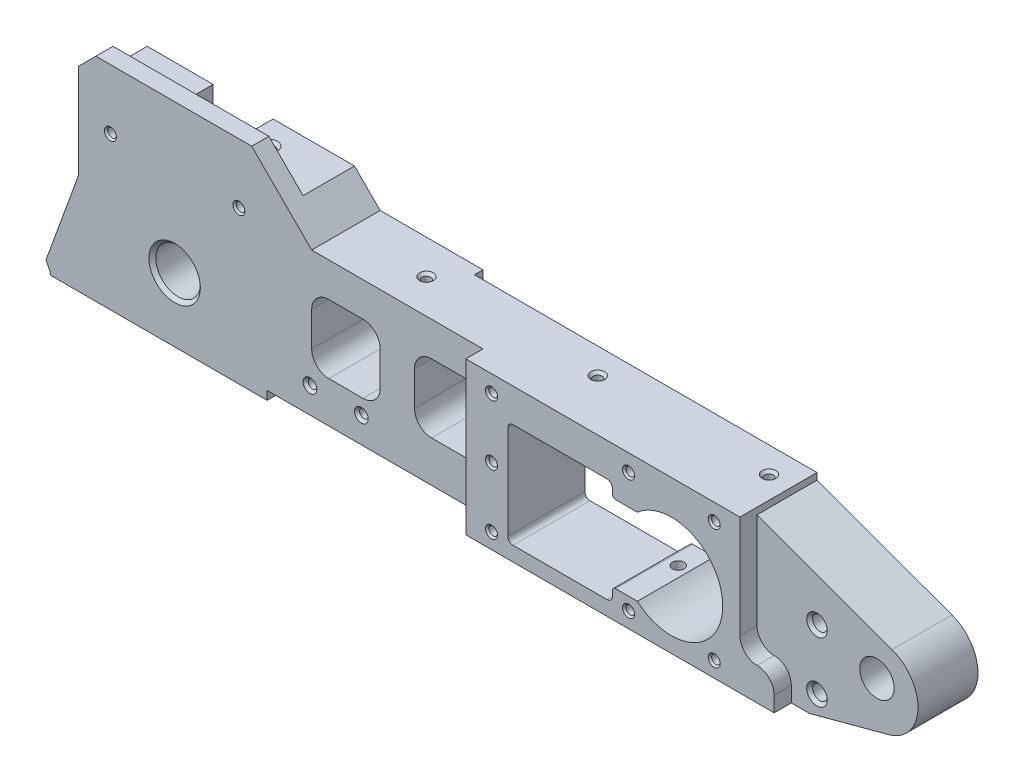
SolidWorks part; units mm, degrees
material "3.0255 (EN-AW 1350A)"
ref_plane "Спереди" through (0, 0, 0) normal (0, 0, 1) x (1, 0, 0)
ref_plane "Сверху" through (0, 0, 0) normal (0, 1, 0) x (1, 0, 0)
ref_plane "Справа" through (0, 0, 0) normal (1, 0, 0) x (0, 0, -1)
sketch "Эскиз5" plane through (0, 0, 0) normal (0, 0, 1) x (1, 0, 0)
  line L1 (45, 40) -> (80, 5)
  line L2 (-56, 40) -> (-56, -25)
  line L3 (-56, -25) -> (-77.8382, -85)
  line L4 (-77.8382, -85) -> (434, -85)
  line L5 (55, 0) -> (-55, 0) construction
  line L6 (434, -85) -> (434, 5)
  line L9 (434, 5) -> (80, 5)
  line L11 (-56, 40) -> (45, 40)
  line L13 (0, -55) -> (0, 55) construction
  circle A0 centre (0, 0) radius 25 construction
  dimension "D6" = 50
  dimension "D2" = 90
  dimension "D3" = 135
  dimension "D4" = 85
  dimension "D7" = 125
  dimension "D8" = 70
  dimension "D9" = 60
  dimension "D10" = 490
  dimension "D11" = 434
  dimension "D12" = 136
extrude "Бобышка-Вытянуть1" add sketch "Эскиз5" along normal mid plane 40
sketch "Эскиз4" plane through (0, 0, -20) normal (0, 0, 1) x (1, 0, 0)
  line L2 (0, 0) -> (0, 50000) construction
  line L4 (-17.5, -25) -> (17.5, -25)
  line L5 (-17.5, 40) -> (-17.5, -25)
  line L6 (45, 40) -> (-56, 40) construction
  line L7 (17.5, 40) -> (17.5, -25)
  point P8 (0, 0)
  line M60 (-56, 40) -> (45, 40)
  dimension "D1" = 35
  dimension "D2" = 65
extrude "Вырез-Вытянуть3" cut sketch "Эскиз4" along normal blind 30 contours L2 L4 L5 M60 | L4 L2 L7 M60 region at (-16.7618, 7.5, -20)
sketch "Эскиз7" plane through (0, 0, 20) normal (0, 0, 1) x (1, 0, 0)
  line L0 (-77.8382, -85) -> (434, -85) construction
  line L1 (434, -85) -> (434, 5) construction
  circle A0 centre (410, -46.6) radius 10.05
  dimension "D3" = 20.1
  dimension "D1" = 38.4
  dimension "D2" = 24
extrude "Вырез-Вытянуть5" cut sketch "Эскиз7" against normal through all
sketch "Эскиз6" plane through (0, 0, 20) normal (0, 0, 1) x (1, 0, 0)
  line L1 (434, 5) -> (80, 5) construction
  line L2 (434, -85) -> (434, 5) construction
  line L3 (434, -26.1873) -> (434, 5)
  line L5 (434, -26.1873) -> (340, 5)
  line L6 (340, 5) -> (434, 5)
  line L7 (410, -46.6) -> (50410, -46.6) construction
  line L8 (434, -67.0127) -> (366.7555, -85)
  line L10 (366.7555, -85) -> (434, -85)
  line L11 (434, -85) -> (434, -67.0127)
  line L12 (-77.8382, -85) -> (434, -85) construction
  line L13 (-56, 40) -> (-56, -25) construction
  dimension "D1" = 396
  dimension "D2" = 31.1873
extrude "Вырез-Вытянуть4" cut sketch "Эскиз6" against normal through all
sketch "Эскиз8" plane through (0, 0, 20) normal (0, 0, 1) x (1, 0, 0)
  line L0 (-77.8382, -85) -> (366.7555, -85) construction
  line L1 (54, -85) -> (354, -85)
  line L2 (54, -85) -> (54, -79)
  line L3 (54, -79) -> (354, -79)
  line L4 (354, -85) -> (354, -79)
  line L5 (-56, 40) -> (-56, -25) construction
  dimension "D1" = 6
  dimension "D2" = 110
  dimension "D3" = 300
extrude "Вырез-Вытянуть6" cut sketch "Эскиз8" against normal through all
sketch "Эскиз9" plane through (0, 0, -20) normal (0, 0, -1) x (-1, 0, 0)
  line L0 (56, 40) -> (56, 20)
  line L1 (56, 40) -> (56, -25) construction
  line L2 (56, 20) -> (-65, 20)
  line L3 (-80, 5) -> (-45, 40) construction
  line L4 (-65, 20) -> (-45, 40)
  line L5 (-45, 40) -> (56, 40)
  dimension "D1" = 20
extrude "Вырез-Вытянуть7" cut sketch "Эскиз9" against normal blind 30
sketch "Эскиз13" plane through (0, 0, -20) normal (0, 0, -1) x (-1, 0, 0)
  line L1 (-204.5, -75.5) -> (-265.5, -75.5)
  line L2 (-204.5, -75.5) -> (-204.5, -14.5)
  line L3 (-204.5, -14.5) -> (-265.5, -14.5)
  line L4 (-265.5, -75.5) -> (-265.5, -67.5)
  line L5 (-204.5, -75.5) -> (-265.5, -14.5) construction
  line L6 (-204.5, -14.5) -> (-265.5, -75.5) construction
  line L7 (-265.5, -22.5) -> (-280.1569, -22.5)
  line L8 (-300, -45) -> (49700, -45) construction
  line L9 (-265.5, -67.5) -> (-280.1569, -67.5)
  line L10 (-265.5, -22.5) -> (-265.5, -14.5)
  arc A0 (-280.1569, -22.5) -> (-280.1569, -67.5) centre (-300, -45) ccw
  circle A1 centre (-235, -45) radius 29 construction
  point P0 (-235, -45)
  point P6 (-235, -45)
  dimension "D7" = 60
  dimension "D8" = 58
  dimension "D1" = 300
  dimension "D2" = 61
  dimension "D3" = 61
  dimension "D4" = 45
  dimension "D5" = 45
  dimension "D6" = 65
extrude "Вырез-Вытянуть8" cut sketch "Эскиз13" against normal through all and the other way through all
sketch "Эскиз16" plane through (0, 0, 20) normal (0, 0, 1) x (1, 0, 0)
  line L0 (410, -46.6) -> (-49590, -46.6) construction
  circle A0 centre (0, -46.6) radius 13
  dimension "D1" = 26
extrude "Вырез-Вытянуть10" cut sketch "Эскиз16" against normal blind 30
sketch "Эскиз19" plane through (0, 0, -20) normal (0, 0, -1) x (-1, 0, 0)
  point P0 (0, -46.6)
sketch "Эскиз14" plane through (0, 0, 20) normal (0, 0, 1) x (1, 0, 0)
  line L0 (265.5, -22.5) -> (280.1569, -22.5) construction
  line L1 (280.1569, -67.5) -> (265.5, -67.5) construction
  line L2 (265.5, -75.5) -> (204.5, -75.5) construction
  line L3 (265.5, -14.5) -> (265.5, -22.5) construction
  line L4 (204.5, -14.5) -> (265.5, -14.5) construction
  line L5 (204.5, -75.5) -> (204.5, -14.5) construction
  line L6 (265.5, -22.5) -> (280.1569, -22.5)
  line L7 (280.1569, -67.5) -> (265.5, -67.5)
  line L8 (265.5, -75.5) -> (204.5, -75.5)
  line L9 (265.5, -14.5) -> (265.5, -22.5)
  line L10 (204.5, -14.5) -> (265.5, -14.5)
  line L11 (204.5, -75.5) -> (204.5, -14.5)
  line L15 (340, 5) -> (434, -26.1873) construction
  line L17 (265.5, -67.5) -> (265.5, -75.5)
  line L18 (340, 5) -> (434, -26.1873) construction
  line L19 (180, -85) -> (340, -85)
  line L20 (340, -65) -> (340, 5)
  line L21 (180, 5) -> (340, 5)
  line L22 (340, 5) -> (80, 5) construction
  line L23 (180, 5) -> (180, -85)
  line L24 (-77.8382, -85) -> (54, -85) construction
  line L25 (340, -65) -> (360, -65)
  line L26 (360, -65) -> (360, -85)
  line L27 (360, -85) -> (340, -85)
  arc A0 (280.1569, -67.5) -> (280.1569, -22.5) centre (300, -45) ccw construction
  arc A1 (280.1569, -67.5) -> (280.1569, -22.5) centre (300, -45) ccw
  dimension "D1" = 180
  dimension "D2" = 20
  dimension "D3" = 20
extrude "Бобышка-Вытянуть6" add sketch "Эскиз14" along normal blind 10 contours L20 L21 L23 L19 L27 L26 L25 | L17 L8 L11 L10 L9 L6 A1 L7
sketch "Эскиз15" plane through (0, 0, -20) normal (0, 0, -1) x (-1, 0, 0)
  line L1 (-324, -85) -> (-434, -85)
  line L2 (-324, -85) -> (-324, 10.3085)
  line L3 (-324, 10.3085) -> (-434, 10.3085)
  line L4 (-434, -85) -> (-434, 10.3085)
  line L5 (-434, -67.0127) -> (-434, -26.1873) construction
  line L6 (-340, 5) -> (-434, -26.1873) construction
  dimension "D1" = 110
extrude "Вырез-Вытянуть9" cut sketch "Эскиз15" against normal blind 5
sketch "Эскиз12" plane through (0, -79, 0) normal (0, -1, 0) x (-1, 0, 0)
  line L2 (-54, 20) -> (-54, -20) construction
  line L4 (-180, -20) -> (-54, -20) construction
  line L5 (-339, 0) -> (49661, 0) construction
  point P0 (-69, -10)
  point P2 (-131.5, 10)
  point P4 (-189, -10)
  point P8 (-339, 0)
  point P39 (-274, 0)
  dimension "D1" = 205
  dimension "D2" = 120
  dimension "D3" = 65
  dimension "D4" = 62.5
  dimension "D5" = 15
  dimension "D6" = 20
  dimension "D7" = 10
hole_wizard "Отверстие обработанное метчиком M87" positions "Эскиз12" profile "Эскиз11" tap size "M8" standard "ISO"
sketch "Эскиз11" plane through (69, -79, 10) normal (1, 0, 0) x (0, 0, -1)
  line L0 (0, 0) -> (0, 27.0429)
  line L1 (0, 27.0429) -> (3.4, 25)
  line L2 (3.4, 25) -> (3.4, 1.6)
  line L3 (3.4, 1.6) -> (5, 0)
  line L5 (5, 0) -> (0, 0)
  line L6 (-3.4, 1.6) -> (-5, 0) construction
  line L10 (0, 27.0429) -> (-3.4, 25) construction
  line L11 (0, -6.35) -> (0, 107.95) construction
  dimension "Диаметр сверла" = 6.8
  dimension "Глубина сверла" = 25
  dimension "Диаметр передней зенковки" = 10
  dimension "Угол передней зенковки" = 90
  dimension "Угол заточки сверла" = 118
cosmetic thread "Отверстие резьбы29" parameters "D1"=20, "D2"=8
cosmetic thread "Отверстие резьбы30" parameters "D1"=20, "D2"=8
cosmetic thread "Отверстие резьбы31" parameters "D1"=20, "D2"=8
cosmetic thread "Отверстие резьбы32" parameters "D1"=20, "D2"=8
cosmetic thread "Отверстие резьбы33" parameters "D1"=20, "D2"=8
sketch "Эскиз22" plane through (0, 0, -20) normal (0, 0, -1) x (-1, 0, 0)
  point P0 (0, -46.6)
hole_wizard "Зенковка для винта с потайной головкой и внутренним шестигранником M101" positions "Эскиз22" profile "Эскиз21" countersink size "M10" standard "DIN" end condition through all
sketch "Эскиз21" plane through (0, -46.6, -20) normal (1, 0, 0) x (0, 1, 0)
  line L0 (0, 0) -> (0, 50)
  line L1 (0, 50) -> (5.5, 50)
  line L2 (5.5, 50) -> (5.5, 5.865)
  line L3 (5.5, 5.865) -> (11.365, 0)
  line L5 (11.365, 0) -> (0, 0)
  line L6 (-5.5, 5.865) -> (-11.365, 0) construction
  line L11 (0, -6.35) -> (0, 107.95) construction
  dimension "Диаметр сквозного отверстия" = 11
  dimension "Глубина сквозного отверстия" = 50
  dimension "Диаметр передней зенковки" = 22.73
  dimension "Угол передней зенковки" = 90
sketch "Эскиз25" plane through (0, 0, 20) normal (0, 0, 1) x (1, 0, 0)
  line L2 (0, 0) -> (0, 50000) construction
  line L3 (45, 40) -> (-56, 40) construction
  point P0 (-37.5, 5)
  point P2 (37.5, 5)
  dimension "D1" = 75
  dimension "D2" = 35
hole_wizard "Отверстие обработанное метчиком M610" positions "Эскиз25" profile "Эскиз24" tap size "M6" standard "DIN"
cosmetic thread "Отверстие резьбы3" parameters "D1"=16, "D2"=6
cosmetic thread "Отверстие резьбы4" parameters "D1"=16, "D2"=6
sketch "Эскиз24" plane through (-37.5, 5, 20) normal (1, 0, 0) x (0, -1, 0)
  line L0 (0, 0) -> (0, 21.5022)
  line L1 (0, 21.5022) -> (2.5, 20)
  line L2 (2.5, 20) -> (2.5, 1)
  line L3 (2.5, 1) -> (3.5, 0)
  line L5 (3.5, 0) -> (0, 0)
  line L6 (-2.5, 1) -> (-3.5, 0) construction
  line L10 (0, 21.5022) -> (-2.5, 20) construction
  line L11 (0, -6.35) -> (0, 107.95) construction
  dimension "Диаметр сверла" = 5
  dimension "Глубина сверла" = 20
  dimension "Диаметр передней зенковки" = 7
  dimension "Угол передней зенковки" = 90
  dimension "Угол заточки сверла" = 118
sketch "Эскиз28" plane through (0, 0, 30) normal (0, 0, 1) x (1, 0, 0)
  line L0 (195, -10.4746) -> (195, -50010.4746) construction
  line L1 (187.4052, -75) -> (50187.4052, -75) construction
  line L2 (184.5162, -5) -> (44922.1769, -5) construction
  line L4 (180, -85) -> (360, -85) construction
  line L5 (325, -23.0261) -> (325, -50023.0261) construction
  line L6 (180, 5) -> (180, -79) construction
  point P0 (195, -5)
  point P15 (195, -40)
  point P17 (275, -5)
  point P19 (325, -5)
  point P26 (325, -75)
  point P28 (275, -75)
  point P40 (195, -75)
  dimension "D1" = 10
  dimension "D2" = 70
  dimension "D3" = 80
  dimension "D4" = 130
  dimension "D5" = 35
  dimension "D6" = 15
hole_wizard "Отверстие обработанное метчиком M64" positions "Эскиз28" profile "Эскиз27" tap size "M6" standard "DIN"
cosmetic thread "Отверстие резьбы5" parameters "D1"=12, "D2"=6
cosmetic thread "Отверстие резьбы6" parameters "D1"=12, "D2"=6
cosmetic thread "Отверстие резьбы7" parameters "D1"=12, "D2"=6
cosmetic thread "Отверстие резьбы10" parameters "D1"=12, "D2"=6
cosmetic thread "Отверстие резьбы11" parameters "D1"=12, "D2"=6
sketch "Эскиз27" plane through (195, -5, 30) normal (1, 0, 0) x (0, -1, 0)
  line L0 (0, 0) -> (0, 16.5022)
  line L1 (0, 16.5022) -> (2.5, 15)
  line L2 (2.5, 15) -> (2.5, 1)
  line L3 (2.5, 1) -> (3.5, 0)
  line L5 (3.5, 0) -> (0, 0)
  line L6 (-2.5, 1) -> (-3.5, 0) construction
  line L10 (0, 16.5022) -> (-2.5, 15) construction
  line L11 (0, -6.35) -> (0, 107.95) construction
  dimension "Диаметр сверла" = 5
  dimension "Глубина сверла" = 15
  dimension "Диаметр передней зенковки" = 7
  dimension "Угол передней зенковки" = 90
  dimension "Угол заточки сверла" = 118
cosmetic thread "Отверстие резьбы22" parameters "D1"=12, "D2"=6
cosmetic thread "Отверстие резьбы23" parameters "D1"=12, "D2"=6
sketch "Эскиз31" plane through (0, 0, -15) normal (0, 0, -1) x (-1, 0, 0)
  line L0 (-324, -79) -> (-324, -63) construction
  line L1 (-354, -79) -> (-324, -79) construction
  point P0 (-352, -64)
  point P2 (-352, -19)
  dimension "D1" = 45
  dimension "D2" = 28
  dimension "D3" = 15
hole_wizard "Отверстие обработанное метчиком M65" positions "Эскиз31" profile "Эскиз30" tap size "M6" standard "DIN"
cosmetic thread "Отверстие резьбы12" parameters "D1"=16, "D2"=6
cosmetic thread "Отверстие резьбы13" parameters "D1"=16, "D2"=6
sketch "Эскиз30" plane through (352, -64, -15) normal (1, 0, 0) x (0, 1, 0)
  line L0 (0, 0) -> (0, 21.5022)
  line L1 (0, 21.5022) -> (2.5, 20)
  line L2 (2.5, 20) -> (2.5, 1.5)
  line L3 (2.5, 1.5) -> (4, 0)
  line L5 (4, 0) -> (0, 0)
  line L6 (-2.5, 1.5) -> (-4, 0) construction
  line L10 (0, 21.5022) -> (-2.5, 20) construction
  line L11 (0, -6.35) -> (0, 107.95) construction
  dimension "Диаметр сверла" = 5
  dimension "Глубина сверла" = 20
  dimension "Диаметр передней зенковки" = 8
  dimension "Угол передней зенковки" = 90
  dimension "Угол заточки сверла" = 118
sketch "Эскиз34" plane through (0, 0, 20) normal (0, 0, 1) x (1, 0, 0)
  line L0 (180, -85) -> (360, -85) construction
  line L1 (340, -65) -> (340, 5) construction
  point P0 (375, -72)
  point P2 (375, -37)
  dimension "D1" = 13
  dimension "D2" = 35
  dimension "D3" = 35
hole_wizard "Отверстие обработанное метчиком M101" positions "Эскиз34" profile "Эскиз33" tap size "M10" standard "DIN"
sketch "Эскиз33" plane through (375, -72, 20) normal (1, 0, 0) x (0, -1, 0)
  line L0 (0, 0) -> (0, 27.5537)
  line L1 (0, 27.5537) -> (4.25, 25)
  line L2 (4.25, 25) -> (4.25, 1.75)
  line L3 (4.25, 1.75) -> (6, 0)
  line L5 (6, 0) -> (0, 0)
  line L6 (-4.25, 1.75) -> (-6, 0) construction
  line L10 (0, 27.5537) -> (-4.25, 25) construction
  line L11 (0, -6.35) -> (0, 107.95) construction
  dimension "Диаметр сверла" = 8.5
  dimension "Глубина сверла" = 25
  dimension "Диаметр передней зенковки" = 12
  dimension "Угол передней зенковки" = 90
  dimension "Угол заточки сверла" = 118
cosmetic thread "Отверстие резьбы14" parameters "D1"=20, "D2"=10
cosmetic thread "Отверстие резьбы15" parameters "D1"=20, "D2"=10
sketch "Эскиз37" plane through (0, 20, 0) normal (0, 1, 0) x (1, 0, 0)
  line L0 (-17.5, 20) -> (-56, 20) construction
  line L2 (0, 0) -> (0, 50000) construction
  point P0 (-30, 5)
  point P2 (30, 5)
  dimension "D1" = 15
  dimension "D2" = 60
hole_wizard "Отверстие обработанное метчиком M83" positions "Эскиз37" profile "Эскиз36" tap size "M8" standard "ISO"
sketch "Эскиз36" plane through (-30, 20, -5) normal (1, 0, 0) x (0, 0, 1)
  line L0 (0, 0) -> (0, 25)
  line L1 (0, 25) -> (3.4, 22.9571)
  line L2 (3.4, 22.9571) -> (3.4, 1.6)
  line L3 (3.4, 1.6) -> (5, 0)
  line L5 (5, 0) -> (0, 0)
  line L6 (-3.4, 1.6) -> (-5, 0) construction
  line L10 (0, 25) -> (-3.4, 22.9571) construction
  line L11 (0, -6.35) -> (0, 107.95) construction
  dimension "Диаметр сверла" = 6.8
  dimension "Глубина сверла" = 25
  dimension "Диаметр передней зенковки" = 10
  dimension "Угол передней зенковки" = 90
  dimension "Угол заточки сверла" = 118
cosmetic thread "Отверстие резьбы16" parameters "D1"=20, "D2"=8
cosmetic thread "Отверстие резьбы17" parameters "D1"=20, "D2"=8
sketch "Эскиз40" plane through (0, -85, 0) normal (0, -1, 0) x (-1, 0, 0)
  point P0 (0, 0)
hole_wizard "Отверстие обработанное метчиком M85" positions "Эскиз40" profile "Эскиз41" tap size "M8" standard "ISO" end condition up to next
sketch "Эскиз41" plane through (0, -85, 0) normal (1, 0, 0) x (0, 0, -1)
  line L0 (0, 0) -> (0, 25.4)
  line L1 (0, 25.4) -> (3.4, 25.4)
  line L2 (3.4, 25.4) -> (3.4, 0)
  line L5 (3.4, 0) -> (0, 0)
  line L11 (0, -6.35) -> (0, 107.95) construction
  dimension "Диаметр проходного сверла" = 6.8
  dimension "Глубина проходного сверла" = 25.4
cosmetic thread "Отверстие резьбы19" parameters "D2"=8
sketch "Эскиз50" plane through (0, 5, 0) normal (0, 1, 0) x (1, 0, 0)
  line L0 (324, 20) -> (80, 20) construction
  line L1 (127, 0) -> (50127, 0) construction
  point P0 (127, 0)
  point P11 (327, 0)
  point P13 (227, 0)
  dimension "D1" = 127
  dimension "D2" = 20
  dimension "D3" = 100
  dimension "D4" = 100
hole_wizard "Отверстие обработанное метчиком M66" positions "Эскиз50" profile "Эскиз49" tap size "M6" standard "ISO"
sketch "Эскиз49" plane through (127, 5, 0) normal (1, 0, 0) x (0, 0, 1)
  line L0 (0, 0) -> (0, 18.5022)
  line L1 (0, 18.5022) -> (2.5, 17)
  line L2 (2.5, 17) -> (2.5, 1.5)
  line L3 (2.5, 1.5) -> (4, 0)
  line L5 (4, 0) -> (0, 0)
  line L6 (-2.5, 1.5) -> (-4, 0) construction
  line L10 (0, 18.5022) -> (-2.5, 17) construction
  line L11 (0, -6.35) -> (0, 107.95) construction
  dimension "Диаметр сверла" = 5
  dimension "Глубина сверла" = 17
  dimension "Диаметр передней зенковки" = 8
  dimension "Угол передней зенковки" = 90
  dimension "Угол заточки сверла" = 118
cosmetic thread "Отверстие резьбы24" parameters "D1"=12, "D2"=6
cosmetic thread "Отверстие резьбы25" parameters "D1"=12, "D2"=6
cosmetic thread "Отверстие резьбы26" parameters "D1"=12, "D2"=6
sketch "Эскиз54" plane through (-41.4144, 15.0736, 0) normal (-0.9397, 0.342, 0) x (0, 0, 1)
  line L0 (20, -106.4961) -> (-20, -106.4961) construction
  line L1 (20, -42.6454) -> (20, -106.4961) construction
  point P0 (0, -86.4961)
  point P7 (0, -61.4961)
  dimension "D1" = 20
  dimension "D2" = 20
  dimension "D3" = 25
hole_wizard "Отверстие обработанное метчиком M86" positions "Эскиз54" profile "Эскиз52" tap size "M8" standard "ISO"
sketch "Эскиз52" plane through (-70.9978, -66.2061, 0) normal (0, 0, 1) x (-0.342, -0.9397, 0)
  line L0 (0, 0) -> (0, 28.0429)
  line L1 (0, 28.0429) -> (3.4, 26)
  line L2 (3.4, 26) -> (3.4, 1.6)
  line L3 (3.4, 1.6) -> (5, 0)
  line L5 (5, 0) -> (0, 0)
  line L6 (-3.4, 1.6) -> (-5, 0) construction
  line L10 (0, 28.0429) -> (-3.4, 26) construction
  line L11 (0, -6.35) -> (0, 107.95) construction
  dimension "Диаметр сверла" = 6.8
  dimension "Глубина сверла" = 26
  dimension "Диаметр передней зенковки" = 10
  dimension "Угол передней зенковки" = 90
  dimension "Угол заточки сверла" = 118
cosmetic thread "Отверстие резьбы27" parameters "D1"=22, "D2"=8
cosmetic thread "Отверстие резьбы28" parameters "D1"=22, "D2"=8
sketch "Эскиз44" plane through (0, -85, 0) normal (0, -1, 0) x (-1, 0, 0)
  point P0 (0, 0)
sketch "Эскиз45" plane through (0, -85, 0) normal (0, -1, 0) x (1, 0, 0)
  circle A0 centre (0, 0) radius 7
extrude "Вырез-Вытянуть11" cut sketch "Эскиз45" against normal blind 10
sketch "Эскиз55" plane through (0, 0, 20) normal (0, 0, 1) x (1, 0, 0)
  line L1 (408.5951, -26.1873) -> (434, -26.1873)
  line L3 (340, 5) -> (434, -26.1873) construction
  line L4 (434, -26.1873) -> (340, 5)
  line L6 (340, -3.4288) -> (408.5951, -26.1873)
  line L7 (340, 5) -> (340, -3.4288)
  line L8 (340, -65) -> (340, 5) construction
  dimension "D1" = 8
extrude "Вырез-Вытянуть12" cut sketch "Эскиз55" against normal through all
sketch "Эскиз56" plane through (0, 0, -20) normal (0, 0, -1) x (-1, 0, 0)
  line L0 (-324, 5) -> (-80, 5) construction
  line L1 (-140, -55) -> (-180, -55)
  line L2 (-140, -55) -> (-140, -15)
  line L3 (-140, -15) -> (-180, -15)
  line L4 (-180, -55) -> (-180, -15)
  line L5 (-140, -55) -> (-180, -15) construction
  line L6 (-140, -15) -> (-180, -55) construction
  line L7 (-80, -55) -> (-120, -55)
  line L8 (-80, -55) -> (-80, -15)
  line L9 (-80, -15) -> (-120, -15)
  line L10 (-120, -55) -> (-120, -15)
  line L11 (-80, -55) -> (-120, -15) construction
  line L12 (-80, -15) -> (-120, -55) construction
  line L13 (56, 20) -> (56, -25) construction
  point P0 (-160, -35)
  point P5 (-100, -35)
  dimension "D1" = 20
  dimension "D2" = 20
  dimension "D3" = 136
  dimension "D4" = 20
  dimension "D5" = 40
  dimension "D6" = 40
extrude "Вырез-Вытянуть13" cut sketch "Эскиз56" against normal through all
sketch "Эскиз64" plane through (0, 5, 0) normal (0, 1, 0) x (1, 0, 0)
  line L0 (324, 15) -> (324, 20)
  line L1 (324, 20) -> (140, 20)
  line L2 (140, 20) -> (140, 15)
  line L3 (140, 15) -> (324, 15)
  line L4 (324, 15) -> (324, 20) construction
  line L5 (324, 20) -> (80, 20) construction
  line L6 (324, 15) -> (340, 15) construction
  line L8 (140, -20) -> (140, 20) construction
extrude "Вырез-Вытянуть16" cut sketch "Эскиз64" against normal through all
fillet "Скругление1" 2 edges at (434, -26.1873, 2.5) (434, -67.0127, 2.5) type full round first side face at (421.2976, -26.1873, 2.5) second side face at (400.3777, -76.0064, 2.5) middle face at (434, -46.6, 2.5)
fillet "Скругление2" radius 10 2 edges at (-17.5, -25, -5) (17.5, -25, -5)
fillet "Скругление3" radius 3 4 edges at (265.5, -75.5, 7.5) (265.5, -14.5, 7.5) (204.5, -14.5, 7.5) (204.5, -75.5, 7.5)
fillet "Скругление4" radius 2 2 edges at (265.5, -67.5, 7.5) (265.5, -22.5, 7.5)
fillet "Скругление5" radius 5 1 edges at (354, -82, 20)
fillet "Скругление6" radius 10 2 edges at (360, -65, 25) (340, -65, 25)
chamfer "Фаска1" distance 10 angle 45 1 edges at (-56, 40, 15)
chamfer "Фаска2" distance 8 angle 45 1 edges at (-77.8382, -85, 0) first distance on face at (-72.7079, -70.9046, 0)
sketch "Эскиз62" plane through (0, 0, 20) normal (0, 0, 1) x (1, 0, 0)
  line L0 (340, -3.4288) -> (340, 1.1402)
  line L1 (340, 1.1402) -> (418.8128, -27.5835)
  line L3 (340, -3.4288) -> (408.5951, -26.1873) construction
  line L4 (340, -55) -> (340, 5) construction
  line L5 (340, -3.4288) -> (408.5951, -26.1873)
  line L6 (408.5951, -26.1873) -> (410.9043, -26.1873) construction
  line L7 (408.5951, -26.1873) -> (410.9043, -26.1873)
  line L8 (416.8724, -71.5942) -> (366.7555, -85) construction
  arc A0 (416.8724, -71.5942) -> (410.9043, -26.1873) centre (410.9043, -49.2829) ccw construction
  arc A1 (418.8128, -27.5835) -> (410.9043, -26.1873) centre (410.9043, -49.2829) ccw
  dimension "D1" = 35
extrude "Бобышка-Вытянуть7" add sketch "Эскиз62" against normal blind 35
ref_plane "Плоскость1" through (0, -45, 0) normal (0, 1, 0) x (1, 0, 0)
ref_plane "Плоскость2" through (300, 0, 0) normal (1, 0, 0) x (0, 0, -1)
ref_plane "Плоскость3" through (235, 0, 0) normal (1, 0, 0) x (0, 0, -1)
ref_axis "Ось2" through (235, -45, 32.5) along (0, 0, -1)
ref_axis "Ось3" through (0, 0, -26.0379) along (0, 0, 1)
fillet "Скругление7" radius 10 8 edges at (120, -55, 0) (80, -55, 0) (80, -15, 0) (120, -15, 0) (140, -55, 2.5) (140, -15, 2.5) (180, -15, 2.5) (180, -55, 2.5)
sketch "Эскиз57" plane through (0, -85, 0) normal (0, -1, 0) x (1, 0, 0)
  line L1 (-101.4836, 68.2425) -> (459.3363, 68.2425)
  line L2 (-101.4836, 68.2425) -> (-101.4836, -42.5625)
  line L3 (-101.4836, -42.5625) -> (459.3363, -42.5625)
  line L4 (459.3363, 68.2425) -> (459.3363, -42.5625)
extrude "Вырез-Вытянуть14" cut sketch "Эскиз57" against normal blind 1
sketch "Эскиз61" plane through (0, 0, 20) normal (0, 0, 1) x (1, 0, 0)
  line L0 (-72.0629, -84) -> (54, -84) construction
  line L1 (-56, 30) -> (-56, -25) construction
  point P0 (79, -64)
  point P3 (109, -64)
  dimension "D1" = 30
  dimension "D2" = 20
  dimension "D3" = 135
hole_wizard "Отверстие обработанное метчиком M69" positions "Эскиз61" profile "Эскиз60" tap size "M6" standard "ISO"
sketch "Эскиз60" plane through (79, -64, 20) normal (1, 0, 0) x (0, -1, 0)
  line L0 (0, 0) -> (0, 21.5022)
  line L1 (0, 21.5022) -> (2.5, 20)
  line L2 (2.5, 20) -> (2.5, 1.5)
  line L3 (2.5, 1.5) -> (4, 0)
  line L5 (4, 0) -> (0, 0)
  line L6 (-2.5, 1.5) -> (-4, 0) construction
  line L10 (0, 21.5022) -> (-2.5, 20) construction
  line L11 (0, -6.35) -> (0, 107.95) construction
  dimension "Диаметр сверла" = 5
  dimension "Глубина сверла" = 20
  dimension "Диаметр передней зенковки" = 8
  dimension "Угол передней зенковки" = 90
  dimension "Угол заточки сверла" = 118
cosmetic thread "Отверстие резьбы34" parameters "D1"=16, "D2"=6
cosmetic thread "Отверстие резьбы35" parameters "D1"=16, "D2"=6
chamfer "Фаска3" distance 2 angle 45 1 edges at (13, -46.6, 20)
